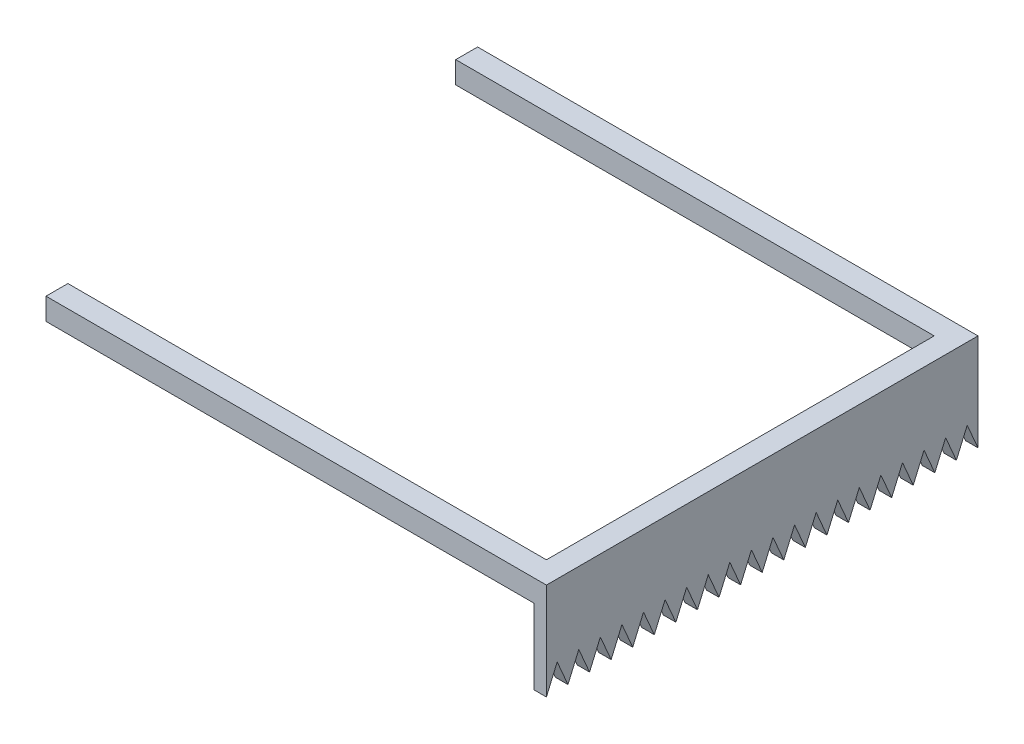
SolidWorks part; units mm, degrees
ref_plane "Front Plane" through (0, 0, 0) normal (0, 0, 1) x (1, 0, 0)
ref_plane "Top Plane" through (0, 0, 0) normal (0, 1, 0) x (1, 0, 0)
ref_plane "Right Plane" through (0, 0, 0) normal (1, 0, 0) x (0, 0, -1)
sketch "Sketch2" plane through (0, 0, 0) normal (1, 0, 0) x (0, 0, -1)
  line L0 (0, 35) -> (0, 0) construction
  line L1 (0, 0) -> (35, 0)
  line L2 (0, 0) -> (0, 35)
  line L3 (0, 35) -> (35, 35)
  line L4 (35, 0) -> (35, 35)
extrude "Boss-Extrude1" add sketch "Sketch2" along normal blind 800
sketch "Sketch3" plane through (0, 0, -35) normal (0, 0, -1) x (-1, 0, 0)
  line L0 (-800, 0) -> (0, 0) construction
  line L1 (-800, 35) -> (-765, 35)
  line L2 (-800, 35) -> (-800, 0)
  line L3 (-800, 0) -> (-765, 0)
  line L4 (-765, 35) -> (-765, 0)
extrude "Boss-Extrude2" add sketch "Sketch3" along normal up to surface (620 mm away)
sketch "Sketch5" plane through (800, 0, 0) normal (1, 0, 0) x (0, 0, -1)
  line L0 (655, 35) -> (0, 35) construction
  line L1 (655, 0) -> (690, 0)
  line L2 (655, 0) -> (655, 35)
  line L3 (655, 35) -> (690, 35)
  line L4 (690, 0) -> (690, 35)
extrude "Boss-Extrude3" add sketch "Sketch5" against normal up to surface (800 mm away) up to face at (0, 17.5, -17.5)
sketch "Sketch6" plane through (0, 0, 0) normal (0, -1, 0) x (1, 0, 0)
  line L0 (0, -690) -> (800, -690) construction
  line L1 (800, 0) -> (780, 0)
  line L2 (800, 0) -> (800, -690)
  line L3 (800, -690) -> (780, -690)
  line L4 (780, 0) -> (780, -690)
  dimension "D1" = 20
extrude "Boss-Extrude4" add sketch "Sketch6" along normal blind 120
sketch "Sketch7" plane through (800, 0, 0) normal (1, 0, 0) x (0, 0, -1)
  line L0 (0, -120) -> (17.25, -80)
  line L1 (17.25, -80) -> (34.5, -120)
  line L2 (690, -120) -> (0, -120) construction
  line L3 (34.5, -120) -> (0, -120)
  line L4 (0, -120) -> (690, -120) construction
  line L5 (17.25, -80) -> (17.25, -120) construction
  line L6 (34.5, -120) -> (51.75, -80)
  line L7 (51.75, -80) -> (69, -120)
  line L8 (69, -120) -> (34.5, -120)
  line L9 (69, -120) -> (86.25, -80)
  line L10 (86.25, -80) -> (103.5, -120)
  line L11 (103.5, -120) -> (69, -120)
  line L12 (103.5, -120) -> (120.75, -80)
  line L13 (120.75, -80) -> (138, -120)
  line L14 (138, -120) -> (103.5, -120)
  line L15 (138, -120) -> (155.25, -80)
  line L16 (155.25, -80) -> (172.5, -120)
  line L17 (172.5, -120) -> (138, -120)
  line L18 (172.5, -120) -> (189.75, -80)
  line L19 (189.75, -80) -> (207, -120)
  line L20 (207, -120) -> (172.5, -120)
  line L21 (207, -120) -> (224.25, -80)
  line L22 (224.25, -80) -> (241.5, -120)
  line L23 (241.5, -120) -> (207, -120)
  line L24 (241.5, -120) -> (258.75, -80)
  line L25 (258.75, -80) -> (276, -120)
  line L26 (276, -120) -> (241.5, -120)
  line L27 (276, -120) -> (293.25, -80)
  line L28 (293.25, -80) -> (310.5, -120)
  line L29 (310.5, -120) -> (276, -120)
  line L30 (310.5, -120) -> (327.75, -80)
  line L31 (327.75, -80) -> (345, -120)
  line L32 (345, -120) -> (310.5, -120)
  line L33 (345, -120) -> (362.25, -80)
  line L34 (362.25, -80) -> (379.5, -120)
  line L35 (379.5, -120) -> (345, -120)
  line L36 (379.5, -120) -> (396.75, -80)
  line L37 (396.75, -80) -> (414, -120)
  line L38 (414, -120) -> (379.5, -120)
  line L39 (414, -120) -> (431.25, -80)
  line L40 (431.25, -80) -> (448.5, -120)
  line L41 (448.5, -120) -> (414, -120)
  line L42 (448.5, -120) -> (465.75, -80)
  line L43 (465.75, -80) -> (483, -120)
  line L44 (483, -120) -> (448.5, -120)
  line L45 (483, -120) -> (500.25, -80)
  line L46 (500.25, -80) -> (517.5, -120)
  line L47 (517.5, -120) -> (483, -120)
  line L48 (517.5, -120) -> (534.75, -80)
  line L49 (534.75, -80) -> (552, -120)
  line L50 (552, -120) -> (517.5, -120)
  line L51 (552, -120) -> (569.25, -80)
  line L52 (569.25, -80) -> (586.5, -120)
  line L53 (586.5, -120) -> (552, -120)
  line L54 (586.5, -120) -> (603.75, -80)
  line L55 (603.75, -80) -> (621, -120)
  line L56 (621, -120) -> (586.5, -120)
  line L57 (621, -120) -> (638.25, -80)
  line L58 (638.25, -80) -> (655.5, -120)
  line L59 (655.5, -120) -> (621, -120)
  line L60 (655.5, -120) -> (672.75, -80)
  line L61 (672.75, -80) -> (690, -120)
  line L62 (690, -120) -> (655.5, -120)
  line L63 (0, -120) -> (34.5, -120) construction
  line M62 (0, -120) -> (690, -120)
  dimension "D1" = 690
  dimension "D2" = 34.5
  dimension "D3" = 40
  dimension "D5" = 34.5
  dimension "D4" = 20
extrude "Cut-Extrude1" cut sketch "Sketch7" against normal through all contours L7 L6 M62 | L10 L9 M62 | L13 L12 M62 | L16 L15 M62 | L19 L18 M62 | L22 L21 M62 | L25 L24 M62 | L28 L27 M62 | L31 L30 M62 | L34 L33 M62 | L37 L36 M62 | L40 L39 M62 | L43 L42 M62 | L46 L45 M62 | L49 L48 M62 | L52 L51 M62 | L55 L54 M62 | L58 L57 M62 | L61 L60 M62 | L1 L3 L0 region at (800, -106.6667, -672.75) region at (800, -106.6667, -638.25) region at (800, -106.6667, -603.75) region at (800, -106.6667, -569.25) region at (800, -106.6667, -534.75) region at (800, -106.6667, -500.25) region at (800, -106.6667, -465.75) region at (800, -106.6667, -431.25) region at (800, -106.6667, -396.75) region at (800, -106.6667, -362.25) region at (800, -106.6667, -327.75) region at (800, -106.6667, -293.25) region at (800, -106.6667, -258.75) region at (800, -106.6667, -224.25) region at (800, -106.6667, -189.75) region at (800, -106.6667, -155.25) region at (800, -106.6667, -120.75) region at (800, -106.6667, -86.25) region at (800, -106.6667, -51.75)
equation "\"D2@Sketch7\" = \"D1@Sketch7\"/20"
equation "\"D5@Sketch7\" = \"D2@Sketch7\""
